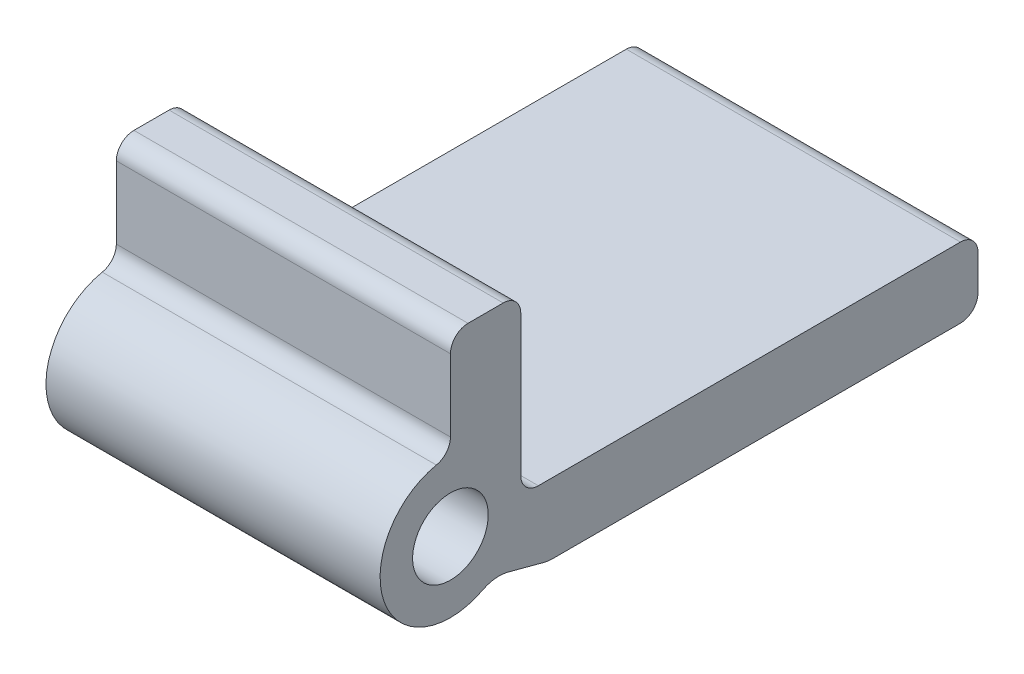
SolidWorks part; units mm, degrees
ref_plane "Front Plane" through (0, 0, 0) normal (0, 0, 1) x (1, 0, 0)
ref_plane "Top Plane" through (0, 0, 0) normal (0, 1, 0) x (1, 0, 0)
ref_plane "Right Plane" through (0, 0, 0) normal (1, 0, 0) x (0, 0, -1)
sketch "Sketch1" plane through (0, 0, 0) normal (1, 0, 0) x (0, 0, -1)
  line L5 (2.4402, -3.1695) -> (5.5539, -4)
  line L15 (5.5539, -4) -> (30, -4)
  line L17 (4, 0) -> (30, 0)
  line L18 (30, -4) -> (30, 0)
  line L19 (0, 10) -> (4, 10)
  line L22 (4, 10) -> (4, 0)
  line L23 (0, 4) -> (0, 10)
  circle A5 centre (0, 0) radius 2.15
  arc A6 (0, 4) -> (2.4402, -3.1695) centre (0, 0) ccw
extrude "Boss-Extrude1" add sketch "Sketch1" along normal mid plane 19
fillet "Fillet1" radius 2 2 edges at (0, -4, -5.5539) (0, -3.1695, -2.4402)
fillet "Fillet2" radius 1 6 edges at (0, -4, -30) (0, 0, -30) (0, 10, -4) (0, 10, 0) (0, 4, 0) (0, 0, -4)
